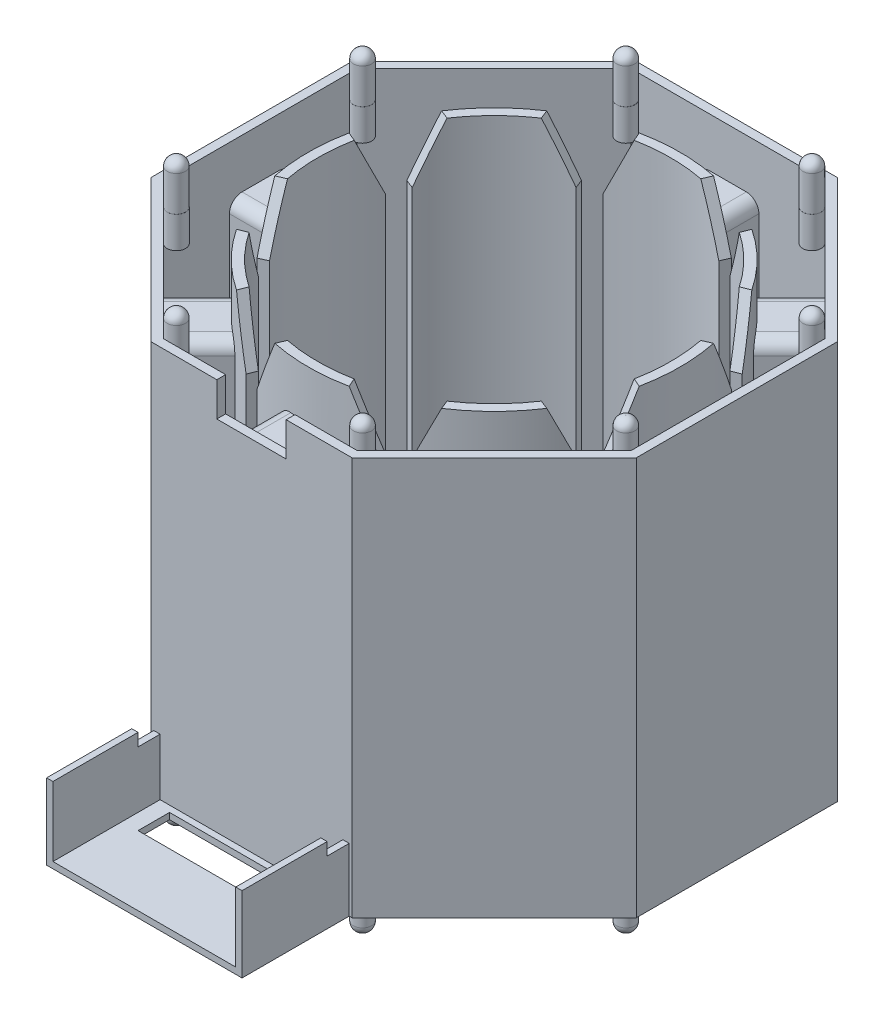
SolidWorks part; units mm, degrees
material "Náilon 101"
ref_plane "Plano frontal" through (0, 0, 0) normal (0, 0, 1) x (1, 0, 0)
ref_plane "Plano superior" through (0, 0, 0) normal (0, 1, 0) x (1, 0, 0)
ref_plane "Plano direito" through (0, 0, 0) normal (1, 0, 0) x (0, 0, -1)
sketch "Esboço1" plane through (0, 0, 0) normal (0, 1, 0) x (1, 0, 0)
  line L0 (18.55, -7.6837) -> (18.55, 7.6837)
  line L1 (19.25, -7.9736) -> (19.25, 7.9736)
  line L2 (19.25, 7.9736) -> (7.9736, 19.25)
  line L3 (7.9736, 19.25) -> (-7.9736, 19.25)
  line L4 (-7.9736, 19.25) -> (-19.25, 7.9736)
  line L5 (-19.25, 7.9736) -> (-19.25, -7.9736)
  line L6 (-19.25, -7.9736) -> (-7.9736, -19.25)
  line L7 (-7.9736, -19.25) -> (7.9736, -19.25)
  line L8 (7.9736, -19.25) -> (19.25, -7.9736)
  line L9 (18.55, 7.6837) -> (7.6837, 18.55)
  line L10 (7.6837, 18.55) -> (-7.6837, 18.55)
  line L11 (-7.6837, 18.55) -> (-18.55, 7.6837)
  line L12 (-18.55, 7.6837) -> (-18.55, -7.6837)
  line L13 (-18.55, -7.6837) -> (-7.6837, -18.55)
  line L14 (-7.6837, -18.55) -> (7.6837, -18.55)
  line L15 (7.6837, -18.55) -> (18.55, -7.6837)
  circle A0 centre (0, 0) radius 19.25 construction
  dimension "D1" = 38.5
  dimension "D2" = 0.7
extrude "Ressalto-extrusão1" add sketch "Esboço1" along normal mid plane 31.6
ref_plane "Plano1" through (0, 11.7, 0) normal (0, 1, 0) x (1, 0, 0)
sketch "Esboço2" plane through (0, 11.7, 0) normal (0, 1, 0) x (1, 0, 0)
  line L0 (-7.6837, 18.55) -> (-18.55, 7.6837) construction
  line L5 (7.6837, 18.55) -> (-7.6837, 18.55) construction
  line L6 (-7.6837, 18.55) -> (-7.896, 18.3377)
  line L7 (-7.3834, 18.55) -> (-7.6837, 18.55)
  line L8 (7.6837, 18.55) -> (7.3834, 18.55)
  line L9 (7.896, 18.3377) -> (7.6837, 18.55)
  line L10 (18.55, 7.6837) -> (18.3377, 7.896)
  line L11 (18.55, 7.3834) -> (18.55, 7.6837)
  line L12 (18.55, -7.6837) -> (18.55, -7.3834)
  line L13 (18.3377, -7.896) -> (18.55, -7.6837)
  line L14 (7.6837, -18.55) -> (7.896, -18.3377)
  line L15 (7.3834, -18.55) -> (7.6837, -18.55)
  line L16 (-7.6837, -18.55) -> (-7.3834, -18.55)
  line L17 (-7.896, -18.3377) -> (-7.6837, -18.55)
  line L18 (-18.55, -7.6837) -> (-18.3377, -7.896)
  line L19 (-18.55, -7.3834) -> (-18.55, -7.6837)
  line L20 (-18.55, 7.6837) -> (-18.55, 7.3834)
  line L21 (-18.3377, 7.896) -> (-18.55, 7.6837)
  arc A0 (-7.896, 18.3377) -> (-7.3834, 18.55) centre (-7.3834, 17.825) ccw
  arc A1 (7.3834, 18.55) -> (7.896, 18.3377) centre (7.3834, 17.825) ccw
  arc A2 (18.3377, 7.896) -> (18.55, 7.3834) centre (17.825, 7.3834) ccw
  arc A3 (18.55, -7.3834) -> (18.3377, -7.896) centre (17.825, -7.3834) ccw
  arc A4 (7.896, -18.3377) -> (7.3834, -18.55) centre (7.3834, -17.825) ccw
  arc A5 (-7.3834, -18.55) -> (-7.896, -18.3377) centre (-7.3834, -17.825) ccw
  arc A6 (-18.3377, -7.896) -> (-18.55, -7.3834) centre (-17.825, -7.3834) ccw
  arc A7 (-18.55, 7.3834) -> (-18.3377, 7.896) centre (-17.825, 7.3834) ccw
  dimension "D2" = 1.45
  dimension "D1" = 8
extrude "Ressalto-extrusão2" add sketch "Esboço2" along normal blind 2.5
sketch "Esboço4" plane through (0, 14.2, 0) normal (0, 1, 0) x (1, 0, 0)
  circle A0 centre (-7.3834, 17.825) radius 0.72
  circle A1 centre (7.3834, 17.825) radius 0.72
  circle A2 centre (17.825, 7.3834) radius 0.72
  circle A3 centre (17.825, -7.3834) radius 0.72
  circle A4 centre (7.3834, -17.825) radius 0.72
  circle A5 centre (-7.3834, -17.825) radius 0.72
  circle A6 centre (-17.825, -7.3834) radius 0.72
  circle A7 centre (-17.825, 7.3834) radius 0.72
  dimension "D1" = 1.44
  dimension "D2" = 8
extrude "Ressalto-extrusão10" add sketch "Esboço4" along normal blind 3.5
fillet "Filete1" radius 0.7 8 edges at (-17.825, 17.7, -6.6634) (-17.825, 17.7, 8.1034) (-7.3834, 17.7, 18.545) (7.3834, 17.7, 18.545) (17.825, 17.7, 8.1034) (17.825, 17.7, -6.6634) (7.3834, 17.7, -17.105) (-7.3834, 17.7, -17.105)
ref_plane "Plano2" through (0, -11.7, 0) normal (0, 1, 0) x (1, 0, 0)
sketch "Esboço5" plane through (0, -11.7, 0) normal (0, 1, 0) x (1, 0, 0)
  line L2 (-18.55, -7.3834) -> (-18.55, -7.6837)
  line L3 (-18.55, -7.6837) -> (-18.3377, -7.896)
  line L4 (-18.55, -7.3834) -> (-18.55, -7.6837)
  line L5 (-18.55, -7.6837) -> (-18.3377, -7.896)
  line L6 (-7.896, -18.3377) -> (-7.6837, -18.55)
  line L7 (-7.6837, -18.55) -> (-7.3834, -18.55)
  line L8 (-7.896, -18.3377) -> (-7.6837, -18.55)
  line L9 (-7.6837, -18.55) -> (-7.3834, -18.55)
  line L10 (7.3834, -18.55) -> (7.6837, -18.55)
  line L11 (7.6837, -18.55) -> (7.896, -18.3377)
  line L12 (7.3834, -18.55) -> (7.6837, -18.55)
  line L13 (7.6837, -18.55) -> (7.896, -18.3377)
  line L14 (18.3377, -7.896) -> (18.55, -7.6837)
  line L15 (18.55, -7.6837) -> (18.55, -7.3834)
  line L16 (18.3377, -7.896) -> (18.55, -7.6837)
  line L17 (18.55, -7.6837) -> (18.55, -7.3834)
  arc A1 (-18.3377, -7.896) -> (-18.55, -7.3834) centre (-17.825, -7.3834) ccw
  arc A2 (-18.3377, -7.896) -> (-18.55, -7.3834) centre (-17.825, -7.3834) ccw
  arc A3 (-7.3834, -18.55) -> (-7.896, -18.3377) centre (-7.3834, -17.825) ccw
  arc A4 (-7.3834, -18.55) -> (-7.896, -18.3377) centre (-7.3834, -17.825) ccw
  arc A5 (7.896, -18.3377) -> (7.3834, -18.55) centre (7.3834, -17.825) ccw
  arc A6 (7.896, -18.3377) -> (7.3834, -18.55) centre (7.3834, -17.825) ccw
  arc A7 (18.55, -7.3834) -> (18.3377, -7.896) centre (17.825, -7.3834) ccw
  arc A8 (18.55, -7.3834) -> (18.3377, -7.896) centre (17.825, -7.3834) ccw
  dimension "D1" = 0
  dimension "D2" = 0
  dimension "D3" = 0
  dimension "D4" = 0
extrude "Ressalto-extrusão11" add sketch "Esboço5" against normal blind 2.5
sketch "Esboço6" plane through (0, -14.2, 0) normal (0, -1, 0) x (1, 0, 0)
  circle A0 centre (-17.825, 7.3834) radius 0.72
  circle A1 centre (-7.3834, 17.825) radius 0.72
  circle A2 centre (7.3834, 17.825) radius 0.72
  circle A3 centre (17.825, 7.3834) radius 0.72
  dimension "D1" = 1.44
extrude "Ressalto-extrusão12" add sketch "Esboço6" along normal blind 3.5
fillet "Filete2" radius 0.7 4 edges at (17.825, -17.7, 6.6634) (7.3834, -17.7, 17.105) (-7.3834, -17.7, 17.105) (-17.825, -17.7, 6.6634)
sketch "Esboço7" plane through (0, 0, 19.25) normal (0, 0, 1) x (1, 0, 0)
  line L0 (7.75, -15.8) -> (-7.75, -15.8)
  line L1 (-7.9736, -15.8) -> (7.9736, -15.8) construction
  line L2 (7.75, -15.8) -> (7.75, -9.8)
  line L4 (-7.75, -9.8) -> (-7.75, -15.8)
  line L5 (-7.25, -9.8) -> (-7.25, -15.3)
  line L6 (7.25, -15.3) -> (-7.25, -15.3)
  line L7 (7.25, -15.3) -> (7.25, -9.8)
  line L8 (-7.75, -9.8) -> (-7.25, -9.8)
  line L9 (7.25, -9.8) -> (7.75, -9.8)
  point P5 (0, -15.8)
  dimension "D1" = 15.5
  dimension "D2" = 6
  dimension "D3" = 0.5
extrude "Ressalto-extrusão13" add sketch "Esboço7" along normal blind 8.5
sketch "Esboço8" plane through (0, 0, 19.25) normal (0, 0, 1) x (1, 0, 0)
  line L0 (-7.9736, 15.8) -> (7.9736, 15.8) construction
  line L1 (-7.9736, 15.8) -> (7.9736, 15.8)
  line L2 (-2.75, 15.8) -> (2.75, 15.8)
  line L3 (-2.75, 15.8) -> (-2.75, 13.1)
  line L4 (-2.75, 13.1) -> (2.75, 13.1)
  line L5 (2.75, 13.1) -> (2.75, 15.8)
  point P5 (0, 15.8)
  dimension "D1" = 5.5
  dimension "D2" = 2.7
extrude "Corte-extrusão1" cut sketch "Esboço8" against normal blind 8.5 and the other way through all contours L4 L5 L1 L3 region at (0, 14.45, 19.25)
sketch "Esboço9" plane through (-18.55, 0, 0) normal (1, 0, 0) x (0, 0, -1)
  line L1 (-1.45, -11.9) -> (1.45, -11.9)
  line L2 (-2.45, -10.9) -> (-2.45, 10.9)
  line L3 (-1.45, 11.9) -> (1.45, 11.9)
  line L4 (2.45, -10.9) -> (2.45, 10.9)
  line L5 (-2.45, -11.9) -> (2.45, 11.9) construction
  line L6 (-2.45, 11.9) -> (2.45, -11.9) construction
  arc A0 (-1.45, -11.9) -> (-2.45, -10.9) centre (-1.45, -10.9) cw
  arc A1 (1.45, -11.9) -> (2.45, -10.9) centre (1.45, -10.9) ccw
  arc A2 (1.45, 11.9) -> (2.45, 10.9) centre (1.45, 10.9) cw
  arc A3 (-2.45, 10.9) -> (-1.45, 11.9) centre (-1.45, 10.9) cw
  point P0 (0, 0)
  dimension "D3" = 1
  dimension "D1" = 4.9
  dimension "D2" = 23.8
extrude "Ressalto-extrusão14" add sketch "Esboço9" along normal blind 4.5
mirror "Espelhar1" about plane through (0, 0, 0) normal (1, 0, 0) of "Ressalto-extrusão14"
sketch "Esboço10" plane through (0, -15.8, 0) normal (0, -1, 0) x (1, 0, 0)
  line L0 (0, 27.75) -> (0, 21.75) construction
  line L1 (-7.75, 27.75) -> (7.75, 27.75) construction
  line L3 (-6, 20.5) -> (6, 20.5)
  line L4 (-6, 20.5) -> (-6, 23)
  line L5 (-6, 23) -> (6, 23)
  line L6 (6, 20.5) -> (6, 23)
  line L7 (-6, 20.5) -> (6, 23) construction
  line L8 (-6, 23) -> (6, 20.5) construction
  dimension "D1" = 6
  dimension "D2" = 2.5
  dimension "D3" = 12
extrude "Corte-extrusão2" cut sketch "Esboço10" against normal through all
sketch "Esboço12" plane through (-13.1168, 0, 13.1168) normal (0.7071, 0, -0.7071) x (-0.7071, 0, -0.7071)
  line L0 (0, -15.8) -> (0, 15.8) construction
  line L1 (-1.45, -11.9) -> (1.45, -11.9)
  line L2 (-2.45, -10.9) -> (-2.45, 10.9)
  line L3 (-1.45, 11.9) -> (1.45, 11.9)
  line L4 (2.45, -10.9) -> (2.45, 10.9)
  line L5 (-2.45, -11.9) -> (2.45, 11.9) construction
  line L6 (-2.45, 11.9) -> (2.45, -11.9) construction
  line L7 (7.6837, -15.8) -> (-7.6837, -15.8) construction
  line L8 (7.6837, 15.8) -> (-7.6837, 15.8) construction
  arc A0 (-1.45, -11.9) -> (-2.45, -10.9) centre (-1.45, -10.9) cw
  arc A1 (1.45, -11.9) -> (2.45, -10.9) centre (1.45, -10.9) ccw
  arc A2 (1.45, 11.9) -> (2.45, 10.9) centre (1.45, 10.9) cw
  arc A3 (-2.45, 10.9) -> (-1.45, 11.9) centre (-1.45, 10.9) cw
  point P0 (-0.1906, 0)
  point P5 (0, 0)
  point P19 (-2.45, 0)
  point P20 (0, 0)
  dimension "D3" = 1
  dimension "D1" = 4.9
  dimension "D2" = 23.8
extrude "Ressalto-extrusão15" add sketch "Esboço12" along normal blind 4.5
sketch "Esboço13" plane through (0, 0, 18.55) normal (0, 0, -1) x (-1, 0, 0)
  line L0 (0, -15.8) -> (0, 15.8) construction
  line L1 (-1.45, -11.9) -> (1.45, -11.9)
  line L2 (-2.45, -10.9) -> (-2.45, 10.9)
  line L3 (-1.45, 11.9) -> (1.45, 11.9)
  line L4 (2.45, -10.9) -> (2.45, 10.9)
  line L5 (-2.45, -11.9) -> (2.45, 11.9) construction
  line L6 (-2.45, 11.9) -> (2.45, -11.9) construction
  line L7 (7.6837, -15.8) -> (-7.6837, -15.8) construction
  arc A0 (-1.45, -11.9) -> (-2.45, -10.9) centre (-1.45, -10.9) cw
  arc A1 (1.45, -11.9) -> (2.45, -10.9) centre (1.45, -10.9) ccw
  arc A2 (1.45, 11.9) -> (2.45, 10.9) centre (1.45, 10.9) cw
  arc A3 (-2.45, 10.9) -> (-1.45, 11.9) centre (-1.45, 10.9) cw
  point P20 (0, 0)
  point P21 (0, 0)
  dimension "D3" = 1
  dimension "D1" = 4.9
  dimension "D2" = 23.8
extrude "Ressalto-extrusão16" add sketch "Esboço13" along normal blind 4.5
sketch "Esboço14" plane through (13.1168, 0, 13.1168) normal (-0.7071, 0, -0.7071) x (-0.7071, 0, 0.7071)
  line L0 (0, -15.8) -> (0, 15.8) construction
  line L1 (-1.45, -11.9) -> (1.45, -11.9)
  line L2 (-2.45, -10.9) -> (-2.45, 10.9)
  line L3 (-1.45, 11.9) -> (1.45, 11.9)
  line L4 (2.45, -10.9) -> (2.45, 10.9)
  line L5 (-2.45, -11.9) -> (2.45, 11.9) construction
  line L6 (-2.45, 11.9) -> (2.45, -11.9) construction
  line L7 (7.6837, -15.8) -> (-7.6837, -15.8) construction
  arc A0 (-1.45, -11.9) -> (-2.45, -10.9) centre (-1.45, -10.9) cw
  arc A1 (1.45, -11.9) -> (2.45, -10.9) centre (1.45, -10.9) ccw
  arc A2 (1.45, 11.9) -> (2.45, 10.9) centre (1.45, 10.9) cw
  arc A3 (-2.45, 10.9) -> (-1.45, 11.9) centre (-1.45, 10.9) cw
  point P0 (-1.4812, -1.217)
  point P18 (0, 0)
  point P19 (0, 0)
  dimension "D3" = 1
  dimension "D1" = 4.9
  dimension "D2" = 23.8
  dimension "D4" = 3.9
extrude "Ressalto-extrusão17" add sketch "Esboço14" along normal blind 4.5
sketch "Esboço15" plane through (13.1168, 0, -13.1168) normal (-0.7071, 0, 0.7071) x (0.7071, 0, 0.7071)
  line L0 (0, -15.8) -> (0, 15.8) construction
  line L1 (-1.45, -11.9) -> (1.45, -11.9)
  line L2 (-2.45, -10.9) -> (-2.45, 10.9)
  line L3 (-1.45, 11.9) -> (1.45, 11.9)
  line L4 (2.45, -10.9) -> (2.45, 10.9)
  line L5 (-2.45, -11.9) -> (2.45, 11.9) construction
  line L6 (-2.45, 11.9) -> (2.45, -11.9) construction
  line L7 (7.6837, -15.8) -> (-7.6837, -15.8) construction
  line L8 (7.6837, 15.8) -> (-7.6837, 15.8) construction
  arc A0 (-1.45, -11.9) -> (-2.45, -10.9) centre (-1.45, -10.9) cw
  arc A1 (1.45, -11.9) -> (2.45, -10.9) centre (1.45, -10.9) ccw
  arc A2 (1.45, 11.9) -> (2.45, 10.9) centre (1.45, 10.9) cw
  arc A3 (-2.45, 10.9) -> (-1.45, 11.9) centre (-1.45, 10.9) cw
  point P0 (-0.6305, -7.6847)
  point P18 (0, 0)
  point P19 (0, 0)
  dimension "D3" = 1
  dimension "D1" = 4.9
  dimension "D2" = 23.8
extrude "Ressalto-extrusão18" add sketch "Esboço15" along normal blind 4.5
sketch "Esboço16" plane through (0, 0, -18.55) normal (0, 0, 1) x (1, 0, 0)
  line L0 (0, -15.8) -> (0, 15.8) construction
  line L1 (-1.45, -11.9) -> (1.45, -11.9)
  line L2 (-2.45, -10.9) -> (-2.45, 10.9)
  line L3 (-1.45, 11.9) -> (1.45, 11.9)
  line L4 (2.45, -10.9) -> (2.45, 10.9)
  line L5 (-2.45, -11.9) -> (2.45, 11.9) construction
  line L6 (-2.45, 11.9) -> (2.45, -11.9) construction
  line L7 (7.6837, -15.8) -> (-7.6837, -15.8) construction
  line L8 (7.6837, 15.8) -> (-7.6837, 15.8) construction
  arc A0 (-1.45, -11.9) -> (-2.45, -10.9) centre (-1.45, -10.9) cw
  arc A1 (1.45, -11.9) -> (2.45, -10.9) centre (1.45, -10.9) ccw
  arc A2 (1.45, 11.9) -> (2.45, 10.9) centre (1.45, 10.9) cw
  arc A3 (-2.45, 10.9) -> (-1.45, 11.9) centre (-1.45, 10.9) cw
  point P0 (0, 0)
  point P18 (0, 0)
  point P20 (0, 0)
  dimension "D3" = 1
  dimension "D1" = 4.9
  dimension "D2" = 23.8
extrude "Ressalto-extrusão19" add sketch "Esboço16" along normal blind 4.5
sketch "Esboço17" plane through (-13.1168, 0, -13.1168) normal (0.7071, 0, 0.7071) x (0.7071, 0, -0.7071)
  line L0 (0, -15.8) -> (0, 15.8) construction
  line L1 (-1.45, -11.9) -> (1.45, -11.9)
  line L2 (-2.45, -10.9) -> (-2.45, 10.9)
  line L3 (-1.45, 11.9) -> (1.45, 11.9)
  line L4 (2.45, -10.9) -> (2.45, 10.9)
  line L5 (-2.45, -11.9) -> (2.45, 11.9) construction
  line L6 (-2.45, 11.9) -> (2.45, -11.9) construction
  line L7 (7.6837, -15.8) -> (-7.6837, -15.8) construction
  arc A0 (-1.45, -11.9) -> (-2.45, -10.9) centre (-1.45, -10.9) cw
  arc A1 (1.45, -11.9) -> (2.45, -10.9) centre (1.45, -10.9) ccw
  arc A2 (1.45, 11.9) -> (2.45, 10.9) centre (1.45, 10.9) cw
  arc A3 (-2.45, 10.9) -> (-1.45, 11.9) centre (-1.45, 10.9) cw
  point P0 (-0.5239, -1.727)
  point P18 (0, 0)
  point P19 (0, 0)
  dimension "D3" = 1
  dimension "D1" = 4.9
  dimension "D2" = 23.8
  dimension "D4" = 3.9
extrude "Ressalto-extrusão20" add sketch "Esboço17" along normal blind 4.5
ref_plane "Plano3" through (0, 15.8, 0) normal (0, 1, 0) x (1, 0, 0)
sketch "Esboço18" plane through (0, 15.8, 0) normal (0, 1, 0) x (1, 0, 0)
  line L6 (0, 0) -> (0, 14) construction
  line L9 (4.596, 13.2241) -> (4.8972, 13.9133)
  line L12 (6.101, 12.6007) -> (6.3754, 13.301)
  line L15 (12.6007, 6.101) -> (13.301, 6.3754)
  line L16 (13.2241, 4.596) -> (13.9133, 4.8972)
  line L19 (13.2241, -4.596) -> (13.9133, -4.8972)
  line L20 (12.6007, -6.101) -> (13.301, -6.3754)
  line L23 (6.101, -12.6007) -> (6.3754, -13.301)
  line L24 (4.596, -13.2241) -> (4.8972, -13.9133)
  line L27 (-4.596, -13.2241) -> (-4.8972, -13.9133)
  line L28 (-6.101, -12.6007) -> (-6.3754, -13.301)
  line L31 (-12.6007, -6.101) -> (-13.301, -6.3754)
  line L32 (-13.2241, -4.596) -> (-13.9133, -4.8972)
  line L35 (-13.2241, 4.596) -> (-13.9133, 4.8972)
  line L36 (-12.6007, 6.101) -> (-13.301, 6.3754)
  line L39 (-6.101, 12.6007) -> (-6.3754, 13.301)
  line L40 (-4.596, 13.2241) -> (-4.8972, 13.9133)
  arc A0 (-6.101, 12.6007) -> (-12.6007, 6.101) centre (0, 0) ccw
  arc A1 (-6.3754, 13.301) -> (-13.301, 6.3754) centre (0, 0) ccw
  arc A2 (4.596, 13.2241) -> (-4.596, 13.2241) centre (0, 0) ccw
  arc A3 (4.8972, 13.9133) -> (-4.8972, 13.9133) centre (0, 0) ccw
  arc A4 (12.6007, 6.101) -> (6.101, 12.6007) centre (0, 0) ccw
  arc A5 (13.301, 6.3754) -> (6.3754, 13.301) centre (0, 0) ccw
  arc A6 (13.9133, -4.8972) -> (13.9133, 4.8972) centre (0, 0) ccw
  arc A7 (13.2241, -4.596) -> (13.2241, 4.596) centre (0, 0) ccw
  arc A8 (6.3754, -13.301) -> (13.301, -6.3754) centre (0, 0) ccw
  arc A9 (6.101, -12.6007) -> (12.6007, -6.101) centre (0, 0) ccw
  arc A10 (-4.596, -13.2241) -> (4.596, -13.2241) centre (0, 0) ccw
  arc A11 (-4.8972, -13.9133) -> (4.8972, -13.9133) centre (0, 0) ccw
  arc A12 (-13.9133, 4.8972) -> (-13.9133, -4.8972) centre (0, 0) ccw
  arc A13 (-13.2241, 4.596) -> (-13.2241, -4.596) centre (0, 0) ccw
  arc A14 (-12.6007, -6.101) -> (-6.101, -12.6007) centre (0, 0) ccw
  arc A15 (-13.301, -6.3754) -> (-6.3754, -13.301) centre (0, 0) ccw
  point P8 (0.8, 0)
  point P9 (0, 14.75)
  point P10 (0.8, 14.75)
  point P11 (-0.8, 0)
  point P12 (-0.8, 14.75)
  dimension "D1" = 28
  dimension "D2" = 29.5
extrude "Ressalto-extrusão21" add sketch "Esboço18" against normal blind 32.6
chamfer "Chanfro1" distance 4.4 distance2 2 16 edges at (-6.2382, 15.8, -12.9509) (-12.9509, 15.8, -6.2382) (-4.7466, 15.8, -13.5687) (4.7466, 15.8, -13.5687) (6.2382, 15.8, -12.9509) (12.9509, 15.8, -6.2382) (13.5687, 15.8, -4.7466) (13.5687, 15.8, 4.7466) (12.9509, 15.8, 6.2382) (6.2382, 15.8, 12.9509) (4.7466, 15.8, 13.5687) (-4.7466, 15.8, 13.5687) (-6.2382, 15.8, 12.9509) (-12.9509, 15.8, 6.2382) (-13.5687, 15.8, 4.7466) (-13.5687, 15.8, -4.7466) first distance on face at (-6.2382, -0.5, -12.9509) first distance on face at (-12.9509, -0.5, -6.2382) first distance on face at (-4.7466, -0.5, -13.5687) first distance on face at (4.7466, -0.5, -13.5687) first distance on face at (6.2382, -0.5, -12.9509) first distance on face at (12.9509, -0.5, -6.2382) first distance on face at (13.5687, -0.5, -4.7466) first distance on face at (13.5687, -0.5, 4.7466) first distance on face at (12.9509, -0.5, 6.2382) first distance on face at (6.2382, -0.5, 12.9509) first distance on face at (4.7466, -0.5, 13.5687) first distance on face at (-4.7466, -0.5, 13.5687) first distance on face at (-6.2382, -0.5, 12.9509) first distance on face at (-12.9509, -0.5, 6.2382) first distance on face at (-13.5687, -0.5, 4.7466) first distance on face at (-13.5687, -0.5, -4.7466)
sketch "Esboço19" plane through (0, -16.8, 0) normal (0, -1, 0) x (1, 0, 0)
  line L1 (1.0945, 13.9571) -> (1.075, 14.7108)
  line L2 (-4.8972, 13.9133) -> (-4.596, 13.2241)
  line L3 (4.596, 13.2241) -> (4.8972, 13.9133)
  line L4 (-4.8972, 13.9133) -> (-4.596, 13.2241)
  line L5 (4.596, 13.2241) -> (4.8972, 13.9133)
  line L6 (-1.0945, 13.9571) -> (-1.075, 14.7108)
  arc A1 (4.596, 13.2241) -> (-4.596, 13.2241) centre (0, 0) ccw construction
  arc A2 (-1.0945, 13.9571) -> (-4.596, 13.2241) centre (0, 0) ccw
  arc A3 (4.8972, 13.9133) -> (-4.8972, 13.9133) centre (0, 0) ccw
  arc A4 (4.596, 13.2241) -> (-4.596, 13.2241) centre (0, 0) ccw
  arc A5 (4.8972, 13.9133) -> (1.075, 14.7108) centre (0, 0) ccw
  arc A6 (4.596, 13.2241) -> (1.0945, 13.9571) centre (0, 0) ccw
  arc A7 (-1.075, 14.7108) -> (-4.8972, 13.9133) centre (0, 0) ccw
  dimension "D1" = 0
extrude "Corte-extrusão3" cut sketch "Esboço19" against normal blind 1
pattern_circular "PadrãoCircular2" count 8 every 45 about axis through (0, -16.8, 0) along (0, -1, 0) of "Corte-extrusão3"
chamfer "Chanfro3" distance 5 distance2 2.9 16 edges at (-6.2382, -15.8, 12.9509) (-12.9509, -15.8, 6.2382) (-13.5687, -15.8, 4.7466) (-13.5687, -15.8, -4.7466) (-12.9509, -15.8, -6.2382) (-6.2382, -15.8, -12.9509) (-4.7466, -15.8, -13.5687) (4.7466, -15.8, -13.5687) (6.2382, -15.8, -12.9509) (12.9509, -15.8, -6.2382) (13.5687, -15.8, -4.7466) (13.5687, -15.8, 4.7466) (12.9509, -15.8, 6.2382) (6.2382, -15.8, 12.9509) (-4.7466, -15.8, 13.5687) (4.7466, -15.8, 13.5687) first distance on face at (-6.2382, -2.2, 12.9509) first distance on face at (-12.9509, -2.2, 6.2382) first distance on face at (-13.5687, -2.2, 4.7466) first distance on face at (-13.5687, -2.2, -4.7466) first distance on face at (-12.9509, -2.2, -6.2382) first distance on face at (-6.2382, -2.2, -12.9509) first distance on face at (-4.7466, -2.2, -13.5687) first distance on face at (4.7466, -2.2, -13.5687) first distance on face at (6.2382, -2.2, -12.9509) first distance on face at (12.9509, -2.2, -6.2382) first distance on face at (13.5687, -2.2, -4.7466) first distance on face at (13.5687, -2.2, 4.7466) first distance on face at (12.9509, -2.2, 6.2382) first distance on face at (6.2382, -2.2, 12.9509) first distance on face at (-4.7466, -2.2, 13.5687) first distance on face at (4.7466, -2.2, 13.5687)
sketch "Esboço21" plane through (0, 0, 20.5) normal (0, 0, 1) x (1, 0, 0)
  line L4 (-6, -15.3) -> (-6, -15.8)
  line L5 (-6, -15.8) -> (6, -15.8)
  line L6 (6, -15.8) -> (6, -15.3)
  line L7 (6, -15.3) -> (-6, -15.3)
  line L8 (-6, -15.3) -> (-6, -15.8)
  line L9 (-6, -15.8) -> (6, -15.8)
  line L10 (6, -15.8) -> (6, -15.3)
  line L11 (6, -15.3) -> (-6, -15.3)
  dimension "D1" = 0
extrude "Corte-extrusão4" cut sketch "Esboço21" against normal blind 0.75
sketch "Esboço22" plane through (0, 0, 23) normal (0, 0, -1) x (-1, 0, 0)
  line L4 (-6, -15.3) -> (-6, -15.8)
  line L5 (-6, -15.8) -> (6, -15.8)
  line L6 (6, -15.8) -> (6, -15.3)
  line L7 (6, -15.3) -> (-6, -15.3)
  line L8 (-6, -15.3) -> (-6, -15.8)
  line L9 (-6, -15.8) -> (6, -15.8)
  line L10 (6, -15.8) -> (6, -15.3)
  line L11 (6, -15.3) -> (-6, -15.3)
  dimension "D1" = 0
extrude "Ressalto-extrusão22" add sketch "Esboço22" along normal blind 0.75
sketch "Esboço23" plane through (0, -9.8, 0) normal (0, 1, 0) x (1, 0, 0)
  line L0 (-13.513, -21) -> (-0.7, -21) construction
  line L1 (-7.75, -21) -> (-7.25, -21)
  line L2 (0.7, -21) -> (13.513, -21) construction
  line L3 (7.25, -21) -> (7.75, -21)
  line L8 (-7.25, -19.25) -> (-7.75, -19.25)
  line L9 (-7.75, -19.25) -> (-7.75, -27.75)
  line L10 (-7.75, -27.75) -> (-7.25, -27.75)
  line L11 (-7.25, -27.75) -> (-7.25, -19.25)
  line L12 (-7.25, -19.25) -> (-7.75, -19.25)
  line L13 (-7.75, -19.25) -> (-7.75, -21)
  line L15 (-7.25, -21) -> (-7.25, -19.25)
  line L16 (7.75, -19.25) -> (7.25, -19.25)
  line L17 (7.25, -19.25) -> (7.25, -27.75)
  line L18 (7.25, -27.75) -> (7.75, -27.75)
  line L19 (7.75, -27.75) -> (7.75, -19.25)
  line L20 (7.75, -19.25) -> (7.25, -19.25)
  line L21 (7.25, -19.25) -> (7.25, -21)
  line L23 (7.75, -21) -> (7.75, -19.25)
  dimension "D1" = 0
  dimension "D2" = 0
extrude "Corte-extrusão5" cut sketch "Esboço23" against normal blind 1
